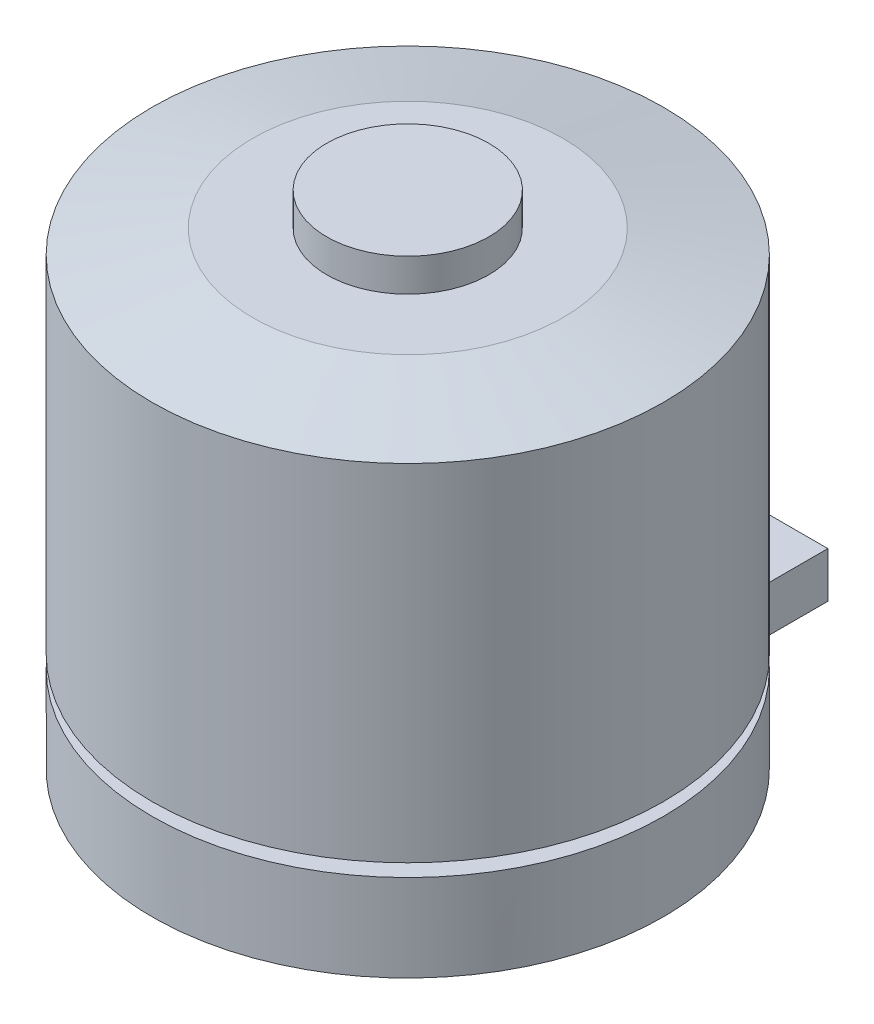
SolidWorks part; units mm, degrees
ref_plane "Front Plane" through (0, 0, 0) normal (0, 0, 1) x (1, 0, 0)
ref_plane "Top Plane" through (0, 0, 0) normal (0, 1, 0) x (1, 0, 0)
ref_plane "Right Plane" through (0, 0, 0) normal (1, 0, 0) x (0, 0, -1)
sketch "Sketch1" plane through (0, 0, 0) normal (0, 0, 1) x (1, 0, 0)
  line L0 (0, 0) -> (0, 29) construction
  line L1 (0, 29) -> (4.44, 29)
  line L2 (4.44, 29) -> (4.44, 27.2)
  line L3 (4.44, 27.2) -> (8.5, 27.2)
  line L4 (8.5, 27.2) -> (14, 25.9302)
  line L5 (14, 25.9302) -> (14, 7)
  line L6 (14, 7) -> (5.67, 7)
  line L7 (5.67, 7) -> (5.67, 6.3)
  line L8 (5.67, 6.3) -> (14, 6.3)
  line L9 (14, 6.3) -> (14, 1.5358)
  line L10 (14, 1.5358) -> (11.34, 0)
  line L11 (11.34, 0) -> (0, 0)
  line L12 (0, 29) -> (0, 0)
  point P16 (5.67, 0)
  dimension "D1" = 14
  dimension "D2" = 29
  dimension "D3" = 1.8
  dimension "D4" = 5.5
  dimension "D5" = 2.66
  dimension "D6" = 0.7
  dimension "D7" = 6.3
  dimension "D8" = 30
  dimension "D9" = 13
  dimension "D10" = 4.44
revolve "Revolve1" add sketch "Sketch1" angle 360 about L0
sketch "Sketch2" plane through (0, 0, 0) normal (0, 0, 1) x (1, 0, 0)
  line L0 (-11.34, 0) -> (11.34, 0) construction
  line L1 (-3, 1) -> (3, 1)
  line L2 (-3, 1) -> (-3, 3.5)
  line L3 (-3, 3.5) -> (3, 3.5)
  line L4 (3, 1) -> (3, 3.5)
  point P4 (0, 1)
  dimension "D1" = 6
  dimension "D2" = 2.5
  dimension "D3" = 1
extrude "Boss-Extrude1" add sketch "Sketch2" against normal blind 20
sketch "Sketch3" plane through (0, 0, 0) normal (0, -1, 0) x (1, 0, 0)
  circle A0 centre (0, 0) radius 3.75
  dimension "D1" = 7.5
extrude "Boss-Extrude2" add sketch "Sketch3" along normal blind 1.66
sketch "Sketch4" plane through (0, -1.66, 0) normal (0, -1, 0) x (1, 0, 0)
  circle A0 centre (0, 0) radius 2
  dimension "D1" = 4
extrude "Boss-Extrude3" add sketch "Sketch4" along normal blind 1
hole_wizard "M3x0.5 Tapped Hole1" positions "Sketch5" profile "Sketch6" tap size "M3x0.5" standard "ANSI Metric"
sketch "Sketch5" plane through (0, 0, 0) normal (0, -1, 0) x (-1, 0, 0)
  line L0 (6.1284, 5.1423) -> (-6.1284, -5.1423) construction
  line L2 (6.1065, -7.2774) -> (-6.1065, 7.2774) construction
  line L4 (3, 20) -> (3, 12.7231) construction
  point P0 (6.1284, 5.1423)
  point P2 (-6.1065, 7.2774)
  point P4 (6.1065, -7.2774)
  point P6 (-6.1284, -5.1423)
  point P14 (0, 0)
  point P19 (0, 0)
  point P20 (5.5142, 5.9888)
  dimension "D1" = 50
  dimension "D2" = 16
  dimension "D3" = 19
sketch "Sketch6" plane through (-6.1284, 0, -5.1423) normal (1, 0, 0) x (0, 0, -1)
  line L0 (0, 0) -> (0, 6.7511)
  line L1 (0, 6.7511) -> (1.25, 6)
  line L2 (1.25, 6) -> (1.25, 0)
  line L5 (1.25, 0) -> (0, 0)
  line L10 (0, 6.7511) -> (-1.25, 6) construction
  line L11 (0, -6.35) -> (0, 107.95) construction
  dimension "Tap Drill Dia." = 2.5
  dimension "Tap Drill Depth" = 6
  dimension "Drill Angle" = 118
cosmetic thread "Hole Thread1" parameters "D1"=6, "D2"=3
cosmetic thread "Hole Thread2" parameters "D1"=6, "D2"=3
cosmetic thread "Hole Thread3" parameters "D1"=6, "D2"=3
cosmetic thread "Hole Thread4" parameters "D1"=6, "D2"=3
